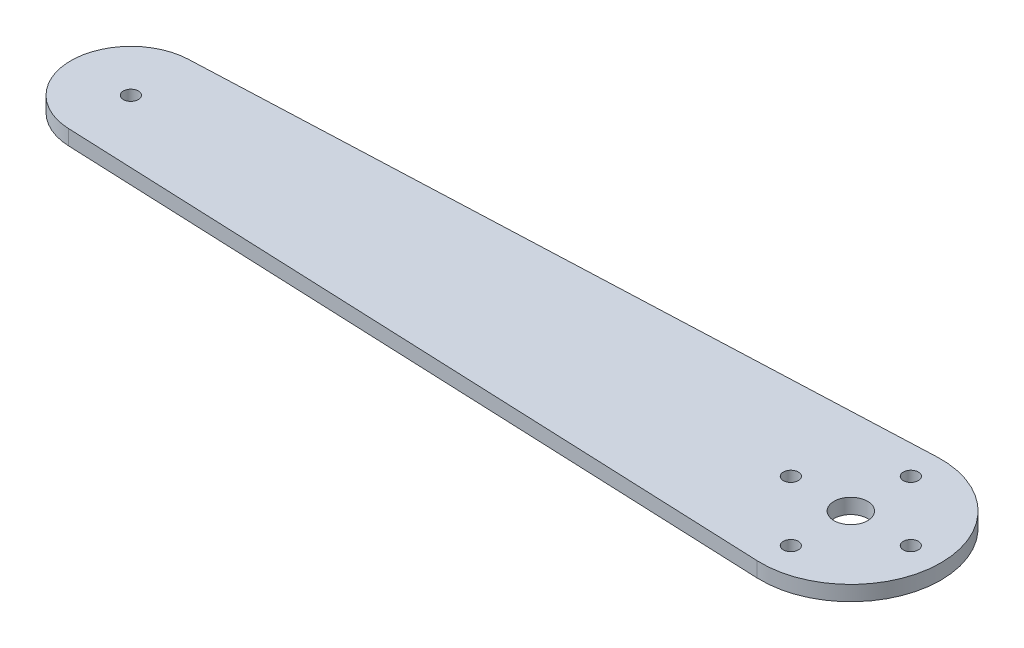
SolidWorks part; units mm, degrees
ref_plane "Front Plane" through (0, 0, 0) normal (0, 0, 1) x (1, 0, 0)
ref_plane "Top Plane" through (0, 0, 0) normal (0, 1, 0) x (1, 0, 0)
ref_plane "Right Plane" through (0, 0, 0) normal (1, 0, 0) x (0, 0, -1)
sketch "Sketch1" plane through (0, 0, 0) normal (0, 1, 0) x (1, 0, 0)
  line L0 (-152.9292, 12.689) -> (-0.7938, 19.0335)
  line L1 (-152.9292, -12.689) -> (-0.7937, -19.0335)
  line L2 (-111.3601, 0) -> (-50111.3601, 0) construction
  line L3 (0, -984.3615) -> (0, 49015.6385) construction
  line L4 (0, 0) -> (0, 12.7) construction
  line L5 (0, 0) -> (12.7, 0) construction
  arc A0 (-0.7937, -19.0335) -> (-0.7938, 19.0335) centre (0, 0) ccw
  arc A1 (-152.9292, 12.689) -> (-152.9292, -12.689) centre (-152.4, 0) ccw
  circle A2 centre (-152.4, 0) radius 1.5875
  circle A3 centre (0, 0) radius 3.556
  circle A4 centre (0, 12.7) radius 1.5875
  circle A5 centre (12.7, 0) radius 1.5875
  circle A6 centre (0, -12.7) radius 1.5875
  circle A7 centre (-12.7, 0) radius 1.5875
  dimension "D1" = 12.7
  dimension "D2" = 19.05
  dimension "D4" = 3.175
  dimension "D5" = 7.112
  dimension "D6" = 3.175
  dimension "D3" = 152.4
  dimension "D7" = 12.7
  dimension "D9" = 90
  dimension "D10" = 12.7
  dimension "D8" = 4
extrude "Boss-Extrude1" add sketch "Sketch1" along normal blind 3.175
